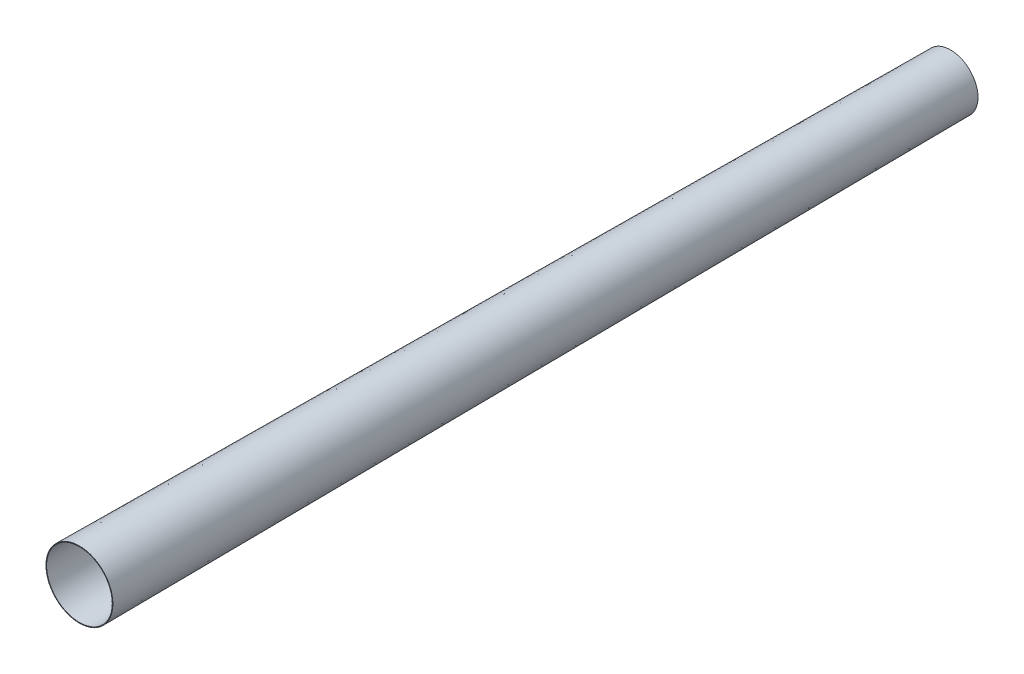
SolidWorks part; units mm, degrees
ref_plane "Front Plane" through (0, 0, 0) normal (0, 0, 1) x (1, 0, 0)
ref_plane "Top Plane" through (0, 0, 0) normal (0, 1, 0) x (1, 0, 0)
ref_plane "Right Plane" through (0, 0, 0) normal (1, 0, 0) x (0, 0, -1)
sketch "Sketch1" plane through (0, 0, 0) normal (0, 0, 1) x (1, 0, 0)
  circle A0 centre (0, 0) radius 21.568
  circle A1 centre (0, 0) radius 22.068
  dimension "D2" = 44.1359
  dimension "D1" = 0.5
ref_plane "Plane1" through (0, 0, 700.9946) normal (0, 0, 1) x (1, 0, 0)
sketch "Sketch2" plane through (0, 0, 700.9946) normal (0, 0, 1) x (1, 0, 0)
  circle A0 centre (0, 0) radius 26.9374
  circle A1 centre (0, 0) radius 26.4374
  dimension "D2" = 53.8748
  dimension "D1" = 0.5
loft "Loft1" add section "Sketch1" section "Sketch2" start constraint default connector at (-19.9618, -9.4086, 0) connector at (-24.4025, -11.4081, 700.9946)
shell "Shell1" thickness 0.5 removed face at (22.068, 0, 0) removed face at (26.9374, 0, 700.9946)
